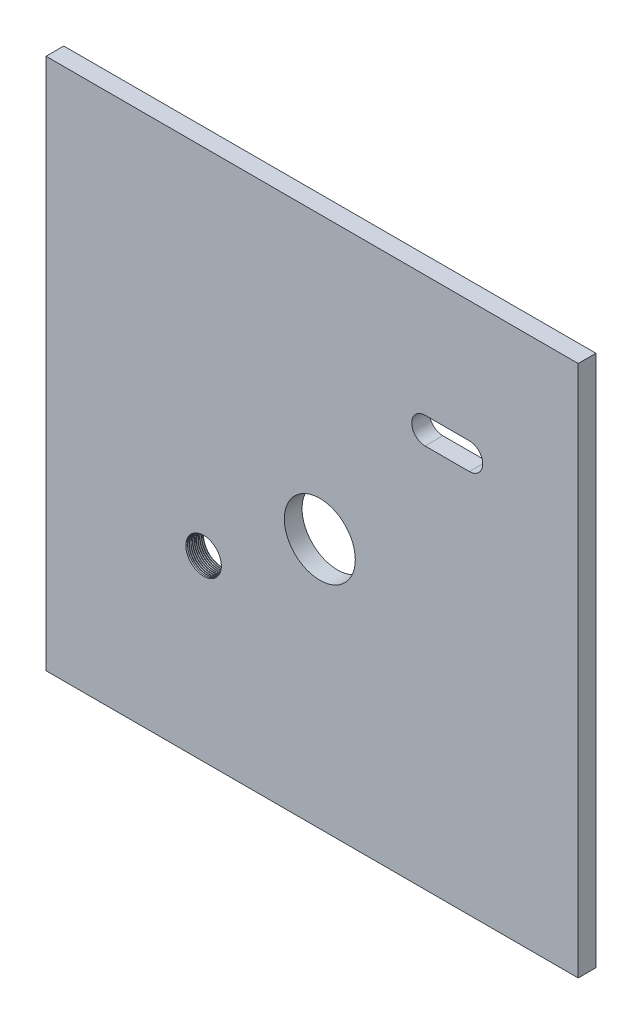
SolidWorks part; units mm, degrees
ref_plane "Front" through (0, 0, 0) normal (0, 0, 1) x (1, 0, 0)
ref_plane "Top" through (0, 0, 0) normal (0, 1, 0) x (1, 0, 0)
ref_plane "Right" through (0, 0, 0) normal (1, 0, 0) x (0, 0, -1)
sketch "Sketch1" plane through (0, 0, 0) normal (0, 0, 1) x (1, 0, 0)
  line L1 (0, 0) -> (-300, 0)
  line L2 (0, 0) -> (0, 300)
  line L3 (0, 300) -> (-300, 300)
  line L4 (-300, 0) -> (-300, 300)
  dimension "D1" = 300
  dimension "D2" = 300
extrude "Boss-Extrude1" add sketch "Sketch1" along normal blind 10
sketch "Sketch4" plane through (0, 0, 10) normal (0, 0, 1) x (1, 0, 0)
  line L0 (-86.3508, 224.0698) -> (-61.3508, 224.0698) construction
  line L1 (-86.3508, 231.5698) -> (-61.3508, 231.5698)
  line L2 (-86.3508, 216.5698) -> (-61.3508, 216.5698)
  circle A0 centre (-211.1774, 100.5637) radius 10
  circle A1 centre (-145.6743, 141.3487) radius 20
  arc A2 (-86.3508, 231.5698) -> (-86.3508, 216.5698) centre (-86.3508, 224.0698) ccw
  arc A3 (-61.3508, 216.5698) -> (-61.3508, 231.5698) centre (-61.3508, 224.0698) ccw
  point P6 (-73.8508, 224.0698)
extrude "Cut-Extrude1" cut sketch "Sketch4" against normal blind 10
thread "Thread1" pitch 1 method cut profile "Thread Profile1" start angle 0, offset 0, length 10, pitch 1, diameter 20
ref_plane "Plane1" through (-221.1774, 100.5637, 10) normal (0, -1, 0) x (-1, 0, 0)
sketch "Thread Profile1" plane through (-221.1774, 100.5637, 10) normal (0, -1, 0) x (-1, 0, 0)
  line L0 (0, 0) -> (0, 1) construction
  line L1 (0, 0) -> (0.5413, 0.3125)
  line L2 (0.5413, 0.3125) -> (0.5413, 0.4375)
  line L3 (0.5413, 0.4375) -> (0, 0.75)
  line L4 (0.5413, 0.375) -> (0, 0.375) construction
  line L11 (0, 0) -> (0, 0.75)
  point P2 (0, 0)
  dimension "Pitch" = 1
  dimension "Profile_Angle" = 60
  dimension "Profile_Land" = 0.125
  dimension "Profile_Height" = 0.5413
